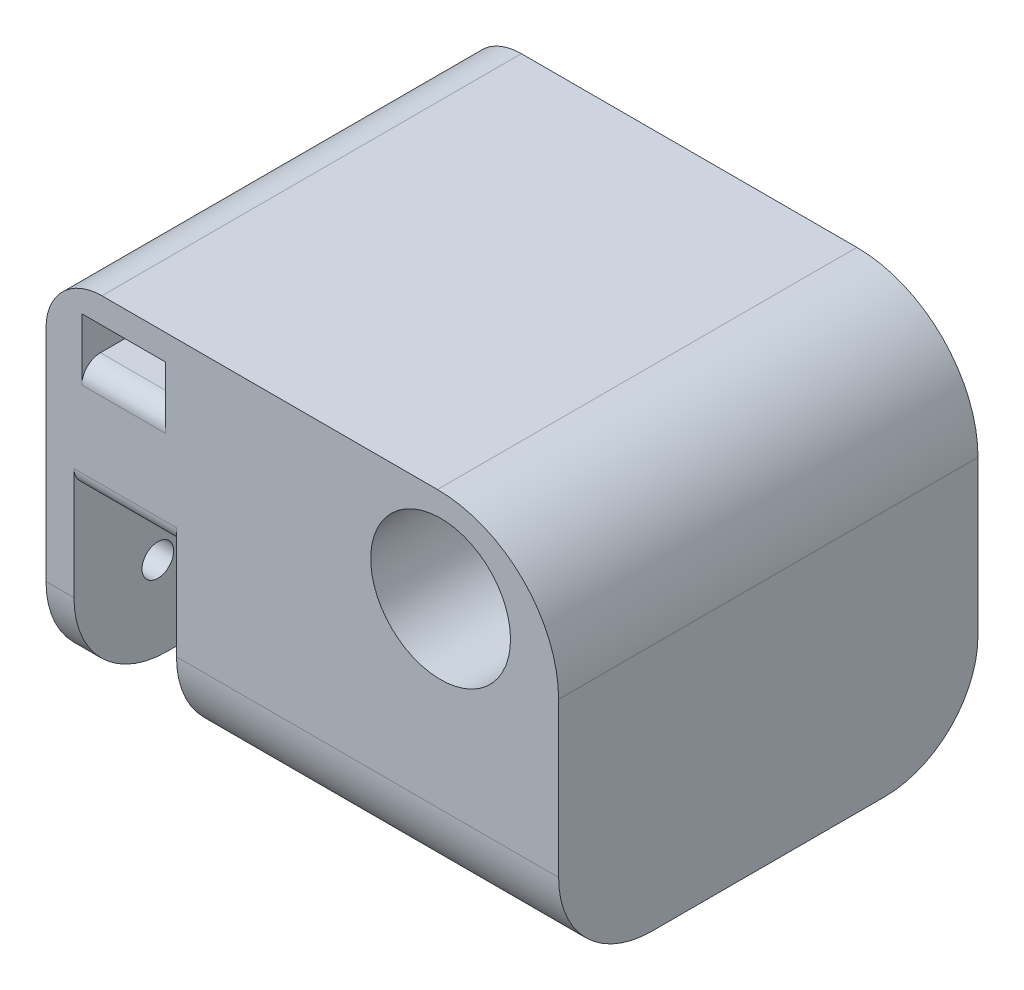
SolidWorks part; units mm, degrees
ref_plane "Front Plane" through (0, 0, 0) normal (0, 0, 1) x (1, 0, 0)
ref_plane "Top Plane" through (0, 0, 0) normal (0, 1, 0) x (1, 0, 0)
ref_plane "Right Plane" through (0, 0, 0) normal (1, 0, 0) x (0, 0, -1)
sketch "Sketch1" plane through (0, 0, 0) normal (0, 0, 1) x (1, 0, 0)
  line L5 (20, 29.55) -> (-35, 29.55)
  line L6 (20, 29.55) -> (20, -10)
  line L7 (20, -10) -> (-35, -10)
  line L8 (-35, 29.55) -> (-35, -10)
  line L9 (20, 29.55) -> (-35, -10) construction
  line L10 (20, -10) -> (-35, 29.55) construction
  circle A0 centre (7.34, 19.55) radius 7.5
  point P0 (-7.5, 9.775)
  dimension "D3" = 15
  dimension "D1" = 55
  dimension "D2" = 39.55
  dimension "D4" = 10
  dimension "D5" = 12.66
extrude "Boss-Extrude1" add sketch "Sketch1" against normal blind 45
sketch "Sketch3" plane through (0, -10, 0) normal (0, -1, 0) x (1, 0, 0)
  line L0 (14.84, 0) -> (-0.16, 0) construction
  line L2 (7.34, 0) -> (7.34, -45) construction
  circle A0 centre (7.34, -11.25) radius 4
  circle A1 centre (7.34, -33.75) radius 4
  point P5 (13.75, 0)
  dimension "D5" = 8
extrude "Cut-Extrude1" cut sketch "Sketch3" against normal blind 9.55
sketch "Sketch4" plane through (0, 0, 0) normal (0, 0, 1) x (1, 0, 0)
  line L0 (-35, -10) -> (20, -10) construction
  line L1 (-32, -10) -> (-21, -10)
  line L2 (-32, -10) -> (-32, 10)
  line L3 (-32, 10) -> (-21, 10)
  line L4 (-21, -10) -> (-21, 10)
  line L5 (-35, 29.55) -> (-35, -10) construction
  dimension "D1" = 20
  dimension "D2" = 11
  dimension "D3" = 3
extrude "Cut-Extrude2" cut sketch "Sketch4" against normal through all
sketch "Sketch5" plane through (-35, 0, 0) normal (-1, 0, 0) x (0, 0, 1)
  line L3 (-45, -10) -> (0, -10) construction
  line L4 (0, 29.55) -> (0, -10) construction
  line L5 (-45, 29.55) -> (-45, -10) construction
  point P0 (-9, -1)
  point P1 (-36, -1)
  dimension "D1" = 9
  dimension "D2" = 9
  dimension "D3" = 9
  dimension "D4" = 9
hole_wizard "M3 Clearance Hole1" positions "3DSketch1" profile "Sketch7" hole size "M3" standard "ISO"
sketch3d "3DSketch1"
  point P0 (-35, -1, -36)
  point P3 (-35, -1, -9)
sketch "Sketch7" plane through (-35, -1, -36) normal (0, 1, 0) x (0, 0, 1)
  line L0 (0, 0) -> (0, 33.0215)
  line L1 (0, 33.0215) -> (1.7, 32)
  line L2 (1.7, 32) -> (1.7, 0.025)
  line L3 (1.7, 0.025) -> (1.725, 0)
  line L5 (1.725, 0) -> (0, 0)
  line L6 (-1.7, 0.025) -> (-1.725, 0) construction
  line L10 (0, 33.0215) -> (-1.7, 32) construction
  line L11 (0, -6.35) -> (0, 107.95) construction
  dimension "Hole Dia." = 3.4
  dimension "Hole Depth" = 32
  dimension "Near C'Sink Dia." = 3.45
  dimension "Near C'Sink Angle" = 90
  dimension "Drill Angle" = 118
sketch "Sketch8" plane through (0, 0, 0) normal (0, 0, 1) x (1, 0, 0)
  line L1 (-31.16, 26.8057) -> (-22.16, 26.8057)
  line L2 (-31.16, 26.8057) -> (-31.16, 22.1785)
  line L3 (-31.16, 22.1785) -> (-22.16, 22.1785)
  line L4 (-22.16, 26.8057) -> (-22.16, 22.1785)
extrude "Cut-Extrude3" cut sketch "Sketch8" against normal through all
fillet "Fillet1" radius 10 4 edges at (-33.5, -10, 0) (-0.5, -10, 0) (-0.5, -10, -45) (-33.5, -10, -45)
fillet "Fillet2" radius 2 4 edges at (-26.66, 22.1785, -45) (-26.66, 22.1785, 0) (-26.5, 10, 0) (-26.5, 10, -45)
fillet "Fillet3" radius 6 1 edges at (-35, 29.55, -22.5)
fillet "Fillet4" radius 13 1 edges at (20, 29.55, -22.5)
